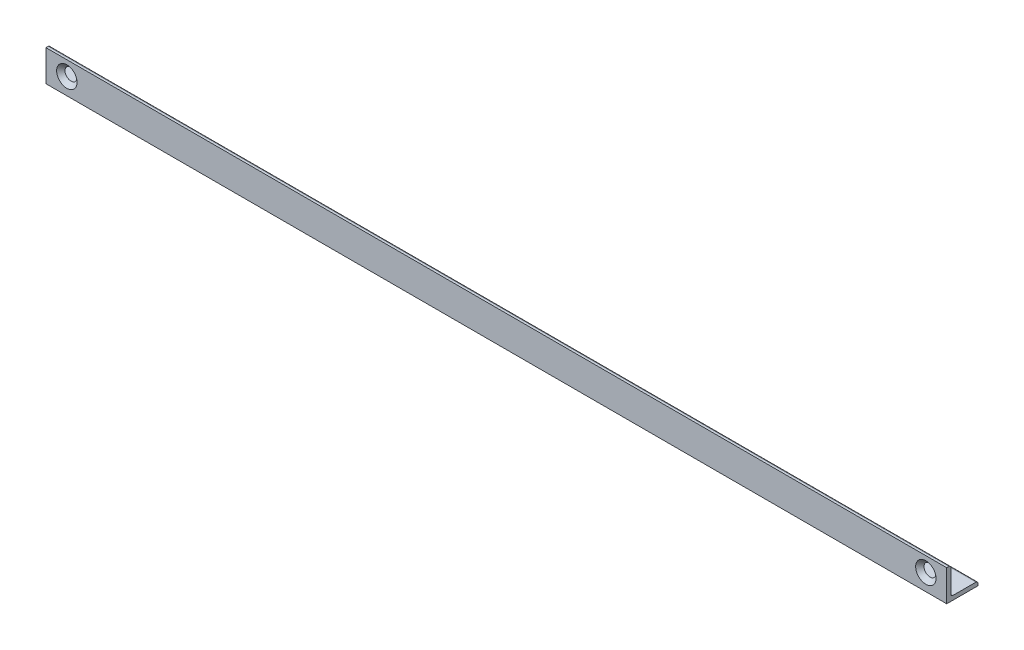
SolidWorks part; units mm, degrees
material "1060 Сплав"
ref_plane "Front" through (0, 0, 0) normal (0, 0, 1) x (1, 0, 0)
ref_plane "Top" through (0, 0, 0) normal (0, 1, 0) x (1, 0, 0)
ref_plane "Right" through (0, 0, 0) normal (1, 0, 0) x (0, 0, -1)
sketch "Эскиз1" plane through (0, 0, 0) normal (1, 0, 0) x (0, 0, -1)
  line L0 (0, 0) -> (0, 15)
  line L1 (0, 0) -> (15, 0)
  line L2 (0, 15) -> (1, 15)
  line L3 (2, 14) -> (2, 3)
  line L4 (3, 2) -> (14, 2)
  line L5 (15, 1) -> (15, 0)
  arc A0 (14, 2) -> (15, 1) centre (14, 1) cw
  arc A1 (1, 15) -> (2, 14) centre (1, 14) cw
  arc A2 (2, 3) -> (3, 2) centre (3, 3) ccw
  point P9 (15, 2)
  point P12 (2, 15)
  dimension "D5" = 1
  dimension "D1" = 15
  dimension "D2" = 15
  dimension "D3" = 2
  dimension "D4" = 2
extrude "Бобышка-Вытянуть1" add sketch "Эскиз1" along normal blind 432
sketch "Эскиз3" plane through (0, 0, -2) normal (0, 0, -1) x (-1, 0, 0)
  line L0 (-432, 3) -> (-432, 14) construction
  line L1 (-432, 15) -> (0, 15) construction
  line L2 (0, 3) -> (0, 14) construction
  circle A0 centre (-407, 8) radius 2.8
  circle A1 centre (-25, 8) radius 2.8
  dimension "D1" = 5.6
  dimension "D2" = 25
  dimension "D3" = 7
  dimension "D4" = 5.6
  dimension "D5" = 7
  dimension "D6" = 25
extrude "Вырез-Вытянуть2" [suppressed] cut sketch "Эскиз3" against normal through all
sketch "Эскиз4" plane through (0, 0, 0) normal (0, -1, 0) x (1, 0, 0)
  line L0 (432, -15) -> (0, -15) construction
  line L1 (0, 0) -> (0, -15) construction
  line L2 (432, 0) -> (432, -15) construction
  circle A0 centre (367, -8) radius 2.25
  circle A2 centre (65, -8) radius 2.25
  dimension "D1" = 4.5
  dimension "D2" = 7
  dimension "D3" = 65
  dimension "D4" = 4.5
  dimension "D5" = 65
  dimension "D6" = 7
extrude "Вырез-Вытянуть3" cut sketch "Эскиз4" against normal blind 2
chamfer "Фаска2" [suppressed] distance 2.098 angle 45
sketch "Эскиз5" [suppressed] plane through (0, 2, 0) normal (0, 1, 0) x (1, 0, 0)
  line L0 (432, 14) -> (432, 3) construction
  line L1 (432, 15) -> (0, 15) construction
  line L2 (0, 14) -> (0, 3) construction
  circle A0 centre (392, 8) radius 2.3
  circle A1 centre (40, 8) radius 2.3
  dimension "D1" = 4.6
  dimension "D2" = 40
  dimension "D3" = 7
  dimension "D4" = 4.6
  dimension "D5" = 7
  dimension "D6" = 40
extrude "Вырез-Вытянуть4" [suppressed] cut sketch "Эскиз5" against normal through all
chamfer "Фаска3" [suppressed] distance 2.05 angle 45
sketch "Эскиз6" [suppressed] plane through (432, 0, 0) normal (1, 0, 0) x (0, 0, -1)
  line L1 (15, 0) -> (2, 0)
  line L2 (15, 0) -> (15, 3)
  line L3 (15, 3) -> (2, 3)
  line L4 (2, 0) -> (2, 3)
extrude "Вырез-Вытянуть5" [suppressed] cut sketch "Эскиз6" against normal blind 15
sketch "Эскиз7" [suppressed] plane through (0, 0, 0) normal (-1, 0, 0) x (0, 0, 1)
  line L1 (-15, 0) -> (-2, 0)
  line L2 (-15, 0) -> (-15, 3)
  line L3 (-15, 3) -> (-2, 3)
  line L4 (-2, 0) -> (-2, 3)
extrude "Вырез-Вытянуть6" [suppressed] cut sketch "Эскиз7" against normal blind 15
sketch "Эскиз8" [suppressed] plane through (0, 0, -2) normal (0, 0, -1) x (-1, 0, 0)
  line L0 (0, 0) -> (0, 5)
  line L1 (0, 0) -> (0, 14) construction
  line L2 (0, 5) -> (-5, 0)
  line L3 (-15, 0) -> (0, 0) construction
  line L4 (-5, 0) -> (0, 0)
  line L5 (-432, 0) -> (-427, 0)
  line L6 (-417, 0) -> (-432, 0) construction
  line L7 (-432, 0) -> (-432, 5)
  line L8 (-432, 0) -> (-432, 14) construction
  line L9 (-432, 5) -> (-427, 0)
  dimension "D1" = 5
  dimension "D2" = 5
  dimension "D3" = 5
  dimension "D4" = 5
extrude "Вырез-Вытянуть7" [suppressed] cut sketch "Эскиз8" against normal through all
sketch "Эскиз9" plane through (0, 0, 0) normal (0, 0, 1) x (1, 0, 0)
  line L0 (432, 15) -> (0, 15) construction
  line L1 (432, 15) -> (432, 0) construction
  line L2 (0, 15) -> (0, 0) construction
  circle A0 centre (422, 8) radius 2.8
  circle A2 centre (10, 8) radius 2.8
  dimension "D1" = 7
  dimension "D2" = 10
  dimension "D3" = 5.6
  dimension "D4" = 7
  dimension "D5" = 10
  dimension "D6" = 5.6
extrude "Вырез-Вытянуть8" cut sketch "Эскиз9" against normal through all
chamfer "Фаска4" distance 2.098 angle 45 2 edges at (12.8, 8, 0) (424.8, 8, 0)
sketch "Эскиз10" [suppressed] plane through (0, 2, 0) normal (0, 1, 0) x (1, 0, 0)
  line L0 (432, 15) -> (0, 15) construction
  line L1 (432, 14) -> (432, 3) construction
  line L2 (0, 14) -> (0, 3) construction
  circle A0 centre (392, 8) radius 2.3
  circle A1 centre (40, 8) radius 2.3
  dimension "D1" = 4.6
  dimension "D2" = 7
  dimension "D3" = 40
  dimension "D4" = 4.6
  dimension "D5" = 7
  dimension "D6" = 40
extrude "Вырез-Вытянуть9" [suppressed] cut sketch "Эскиз10" against normal through all
chamfer "Фаска5" [suppressed] distance 2.05 angle 45
